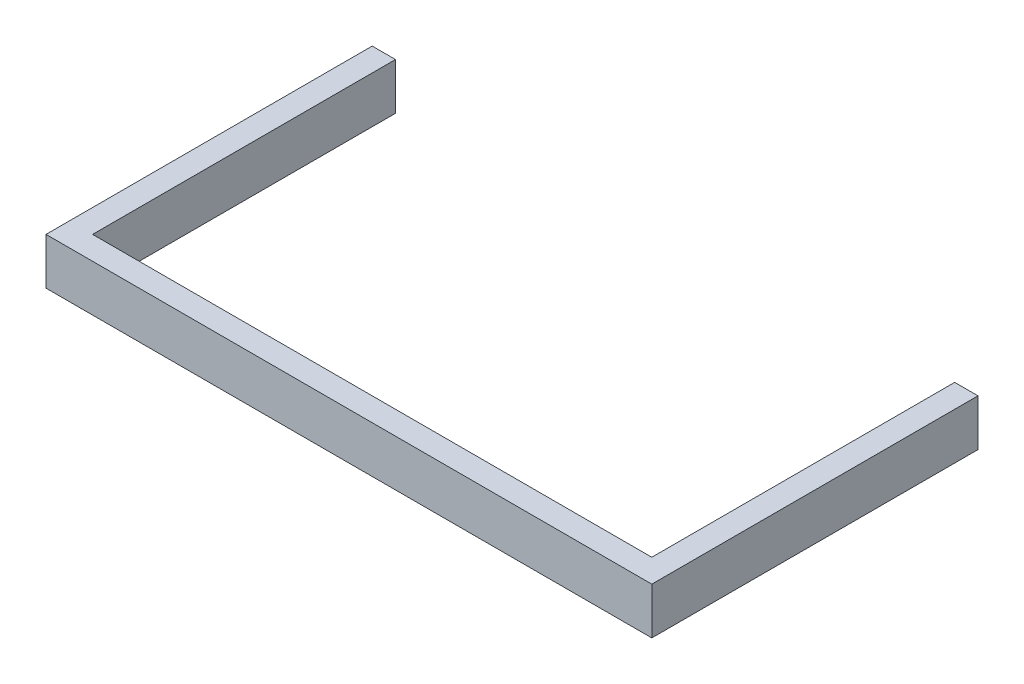
SolidWorks part; units mm, degrees
ref_plane "Front Plane" through (0, 0, 0) normal (0, 0, 1) x (1, 0, 0)
ref_plane "Top Plane" through (0, 0, 0) normal (0, 1, 0) x (1, 0, 0)
ref_plane "Right Plane" through (0, 0, 0) normal (1, 0, 0) x (0, 0, -1)
sketch "Sketch1" plane through (0, 0, 0) normal (0, 1, 0) x (1, 0, 0)
  line L1 (0, 0) -> (660.4, 0)
  line L2 (0, 0) -> (0, 25.4)
  line L3 (25.4, 25.4) -> (166.006, 25.4)
  line L4 (660.4, 0) -> (660.4, 25.4)
  line L5 (0, 0) -> (25.4, 0)
  line L6 (0, 0) -> (0, 355.6)
  line L7 (0, 355.6) -> (25.4, 355.6)
  line L8 (25.4, 25.4) -> (25.4, 339.6476)
  line L9 (660.4, 0) -> (635, 0)
  line L10 (660.4, 0) -> (660.4, 355.6)
  line L11 (660.4, 355.6) -> (635, 355.6)
  line L12 (635, 25.4) -> (635, 339.6476)
  line L14 (46.7473, 355.6) -> (25.4, 355.6)
  line L15 (196.9175, 25.4) -> (166.006, 25.4)
  line L16 (613.6527, 355.6) -> (635, 355.6)
  line L19 (494.394, 25.4) -> (635, 25.4)
  line L20 (196.9175, 25.4) -> (463.4825, 25.4)
  line L21 (25.4, 339.6476) -> (25.4, 355.6)
  line L22 (635, 339.6476) -> (635, 355.6)
  line L23 (463.4825, 25.4) -> (494.394, 25.4)
  point P8 (12.7, 355.6)
  dimension "D1" = 660.4
  dimension "D2" = 330.2
  dimension "D3" = 25.4
  dimension "D4" = 330.2
  dimension "D5" = 25.4
  dimension "D6" = 314.2476
  dimension "D7" = 25.4
  dimension "D9" = 330.2
extrude "Boss-Extrude1" add sketch "Sketch1" along normal blind 50.8 contours L23 L20 L15 L3 L8 L21 L7 L6 L2 L1 L4 L10 L11 L22 L12 L19 region at (7.5005, 0, -12.7)
